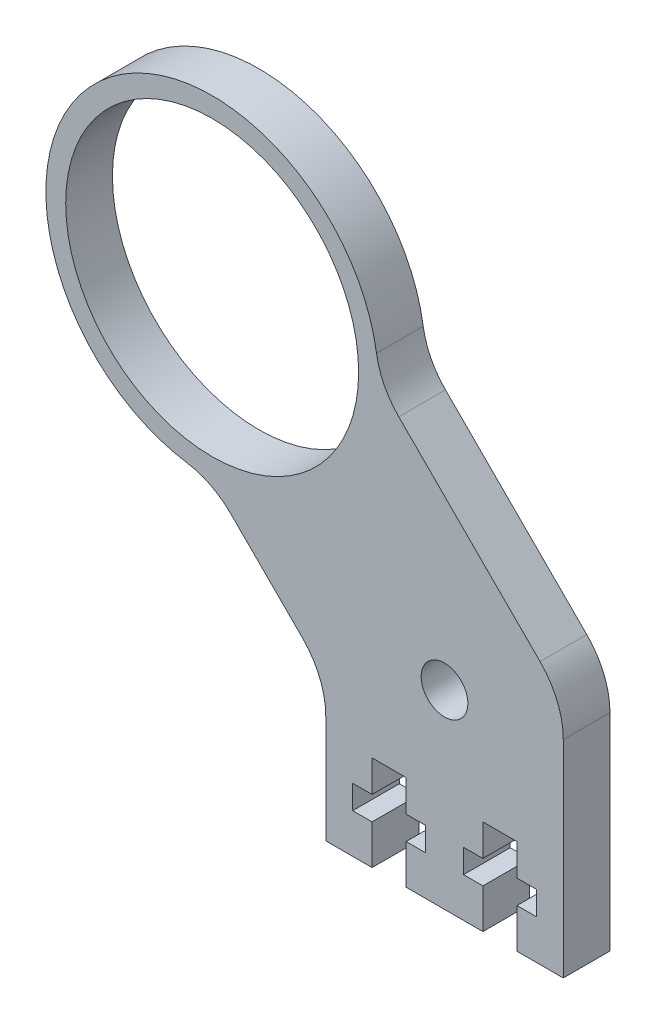
SolidWorks part; units mm, degrees
ref_plane "Front Plane" through (0, 0, 0) normal (0, 0, 1) x (1, 0, 0)
ref_plane "Top Plane" through (0, 0, 0) normal (0, 1, 0) x (1, 0, 0)
ref_plane "Right Plane" through (0, 0, 0) normal (1, 0, 0) x (0, 0, -1)
sketch "Sketch1" plane through (0, 0, 0) normal (0, 0, 1) x (1, 0, 0)
  line L0 (0, 0) -> (-29.3449, 29.3449) construction
  line L1 (0, 0) -> (0, 31.0325) construction
  line L2 (-15, -6.2132) -> (-15, -24)
  line L3 (-15, -24) -> (15, -24)
  line L4 (15, -24) -> (15, 6.2132)
  line L5 (0, 0) -> (0, -24) construction
  line L6 (15, 6.2132) -> (-8.346, 29.5592)
  line L7 (-15, -6.2132) -> (-29.5592, 8.346)
  line L8 (10.6066, 10.6066) -> (-18.7383, 39.9515) construction
  line L9 (-10.6066, -10.6066) -> (-39.9515, 18.7383) construction
  circle A0 centre (0, 0) radius 2.95
  arc A1 (-8.346, 29.5592) -> (-29.5592, 8.346) centre (-29.3449, 29.3449) ccw
  dimension "D1" = 5.9
  dimension "D3" = 42
  dimension "D2" = 41.5
  dimension "D4" = 45
  dimension "D5" = 24
  dimension "D6" = 30
  dimension "D7" = 15
  dimension "D8" = 15
extrude "Boss-Extrude1" add sketch "Sketch1" along normal blind 5.9
sketch "Sketch2" plane through (0, 0, 5.9) normal (0, 0, 1) x (1, 0, 0)
  circle A0 centre (-29.3449, 29.3449) radius 18.5
  dimension "D1" = 37
extrude "Cut-Extrude1" cut sketch "Sketch2" against normal through all
sketch "Sketch3" plane through (0, 0, 5.9) normal (0, 0, 1) x (1, 0, 0)
  line L0 (-15, -24) -> (15, -24) construction
  line L1 (-9.15, -24) -> (-4.85, -24)
  line L2 (-9.15, -24) -> (-9.15, -19)
  line L3 (-9.15, -12) -> (-4.85, -12)
  line L4 (-4.85, -24) -> (-4.85, -19)
  line L5 (0, 0) -> (0, -24) construction
  line L6 (-4.85, -16) -> (-2.4, -16)
  line L7 (-11.6, -16) -> (-9.15, -16)
  line L8 (-11.6, -16) -> (-11.6, -19)
  line L9 (-11.6, -19) -> (-9.15, -19)
  line L10 (-2.4, -16) -> (-2.4, -19)
  line L11 (-9.15, -16) -> (-9.15, -12)
  line L12 (-4.85, -19) -> (-2.4, -19)
  line L13 (-4.85, -16) -> (-4.85, -12)
  line L14 (4.85, -16) -> (4.85, -12)
  line L15 (4.85, -19) -> (2.4, -19)
  line L16 (9.15, -16) -> (9.15, -12)
  line L17 (2.4, -16) -> (2.4, -19)
  line L18 (11.6, -19) -> (9.15, -19)
  line L19 (11.6, -16) -> (11.6, -19)
  line L20 (11.6, -16) -> (9.15, -16)
  line L21 (4.85, -16) -> (2.4, -16)
  line L22 (4.85, -24) -> (4.85, -19)
  line L23 (9.15, -12) -> (4.85, -12)
  line L24 (9.15, -24) -> (9.15, -19)
  line L25 (9.15, -24) -> (4.85, -24)
  point P6 (-7, -12)
  point P18 (-10.375, -19)
  dimension "D1" = 4.3
  dimension "D2" = 7
  dimension "D3" = 12
  dimension "D4" = 9.2
  dimension "D5" = 3
  dimension "D6" = 5
extrude "Cut-Extrude2" cut sketch "Sketch3" against normal through all
fillet "Fillet1" radius 10 4 edges at (-8.346, 29.5592, 2.95) (15, 6.2132, 2.95) (-15, -6.2132, 2.95) (-29.5592, 8.346, 2.95)
equation "\"smallPulleyTeeth\"= 15"
equation "\"largePulleyTeeth\"= 30"
equation "\"eighthThick\"= 2.9mm"
equation "\"sixteenthThick\" = 1.7mm"
equation "\"quarterThick\"=5.9mm"
equation "\"OD\" = 145mm"
equation "\"puckAngle\" = 60.5deg"
equation "\"puckDiam\" = 76.5mm"
equation "\"axlePress\" = 5.9mm"
equation "\"D1@Sketch1\"=\"axlePress\""
equation "\"D1@Boss-Extrude1\"=\"quarterThick\""
equation "\"press\" = 0.2mm"
equation "\"wheelClear\" = 0.3mm"
equation "\"10-32clear\" = 4.5mm"
equation "\"D1@Sketch3\"=\"10-32clear\"-\"press\""
equation "\"6-32clear\" = 3.3mm"
equation "\"8-32clear\" = 4.0mm"
equation "\"wheelHeight\" = 24mm"
equation "\"D5@Sketch1\"=\"wheelHeight\""
